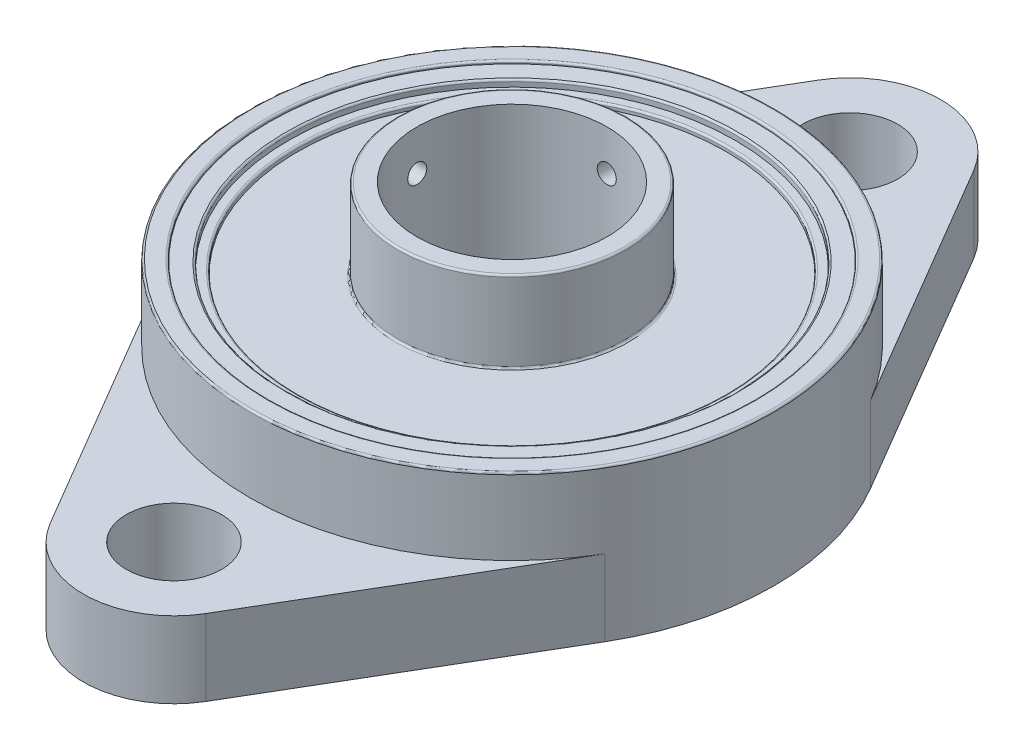
SolidWorks part; units mm, degrees
ref_plane "Front Plane" through (0, 0, 0) normal (0, 0, 1) x (1, 0, 0)
ref_plane "Top Plane" through (0, 0, 0) normal (0, 1, 0) x (1, 0, 0)
ref_plane "Right Plane" through (0, 0, 0) normal (1, 0, 0) x (0, 0, -1)
sketch "Sketch1" plane through (0, 0, 0) normal (0, 1, 0) x (1, 0, 0)
  line L0 (0, -45) -> (0, 45) construction
  line L1 (0, 0) -> (-50000, 0) construction
  line L2 (23.7028, -13.9437) -> (8.1883, -40.3169)
  line L3 (23.7028, 13.9437) -> (8.1883, 40.3169)
  line L4 (-23.7028, -13.9437) -> (-8.1883, -40.3169)
  line L5 (-23.7028, 13.9437) -> (-8.1883, 40.3169)
  circle A0 centre (0, 0) radius 27.5
  circle A1 centre (0, 0) radius 10
  circle A2 centre (0, 35.5) radius 5
  circle A3 centre (0, 0) radius 25.5
  circle A4 centre (0, 0) radius 12
  arc A5 (8.1883, 40.3169) -> (-8.1883, 40.3169) centre (0, 35.5) ccw
  circle A6 centre (0, -35.5) radius 5
  arc A7 (-8.1883, -40.3169) -> (8.1883, -40.3169) centre (0, -35.5) ccw
  circle A8 centre (0, 0) radius 23.5
  circle A9 centre (0, 0) radius 22.5
  point P6 (0, 0)
  dimension "D1" = 20
  dimension "D2" = 55
  dimension "D5" = 10
  dimension "D3" = 90
  dimension "D4" = 71
  dimension "D6" = 2
  dimension "D7" = 2
  dimension "D8" = 2
  dimension "D9" = 1
extrude "A1" add sketch "Sketch1" along normal blind 8 contours L4 A7 L2 A0 A6 | A0 A3 | L3 A5 L5 A0 A2 region at (15.4571, 0, 26.8429) region at (0, 0, 26.7222) region at (-15.4571, 0, -26.8429)
extrude "A" add sketch "Sketch1<3>" along normal blind 16 contours A0 A3 region at (0, 0, 26.7222)
sketch "Sketch1<3>" plane through (0, 0, 0) normal (0, 1, 0) x (1, 0, 0) same geometry as "Sketch1"
extrude "A0" add sketch "Sketch1<4>" along normal blind 23 contours A4 A1 region at (-11.6606, 0, 0)
sketch "Sketch1<4>" plane through (0, 0, 0) normal (0, 1, 0) x (1, 0, 0) same geometry as "Sketch1"
extrude "Bearing outer d" add sketch "Sketch1<7>" along normal blind 13 from offset 2 separate body contours A8 A9 region at (-22.8353, 0, 0)
sketch "Sketch1<7>" plane through (0, 0, 0) normal (0, 1, 0) x (1, 0, 0) same geometry as "Sketch1"
extrude "Boss-Extrude6" add sketch "Sketch1<8>" along normal blind 14.5 from offset 1.2 contours A3 A8 region at (-24.7788, 0, 0)
sketch "Sketch1<8>" plane through (0, 0, 0) normal (0, 1, 0) x (1, 0, 0) same geometry as "Sketch1"
extrude "Boss-Extrude7" add sketch "Sketch1<9>" along normal blind 13 from offset 1.5 contours A9 A4 region at (-21.8636, 0, 0)
sketch "Sketch1<9>" plane through (0, 0, 0) normal (0, 1, 0) x (1, 0, 0) same geometry as "Sketch1"
sketch "Sketch2" plane through (0, 0, 0) normal (1, 0, 0) x (0, 0, -1)
  line L0 (0, 0) -> (0, 50000) construction
  line L1 (-13.9437, 0) -> (13.9437, 0) construction
  line L2 (12, 18.75) -> (-12, 18.75) construction
  line L3 (12, 14.5) -> (12, 23) construction
  line L4 (-12, 23) -> (-12, 14.5) construction
  circle A0 centre (0, 18.75) radius 1
  point P4 (0, 0)
  dimension "D1" = 2
extrude "Cut-Extrude1" cut sketch "Sketch2" against normal up to next
sketch "Sketch3" plane through (0, 0, 0) normal (0, 0, 1) x (1, 0, 0)
  line L0 (0, 0) -> (0, 50000) construction
  line L1 (6, 18.75) -> (-49994, 18.75) construction
  line L3 (12, 14.5) -> (12, 23) construction
  circle A0 centre (0, 18.75) radius 1
  point P7 (12, 18.75)
  point P10 (0, 9.9)
  dimension "D1" = 2
extrude "Cut-Extrude2" cut sketch "Sketch3" against normal up to next
fillet "Fillet1" radius 0.2 1 edges at (0, 15, 22.5)
fillet "Fillet2" radius 0.2 5 edges at (0, 23, 12) (0, 14.5, 12) (0, 16, 27.5) (0, 16, 25.5) (0, 15.7, 23.5)
equation "\"A\"= \"D1@A\""
equation "\"A0\"= \"D1@A0\""
equation "\"A1\"= \"D1@A1\""
equation "\"D1@Bearing outer d\"=\"D1@Boss-Extrude6\" - 1.5"
equation "\"D1@Boss-Extrude6\"=\"D1@A\" - 1.5"
equation "\"D1@Boss-Extrude7\"= \"D1@Bearing outer d\""
equation "\"S\"= \"D19@Boss-Extrude7\""
equation "\"D19@Boss-Extrude6\"=\"D19@Boss-Extrude7\" - 0.3"
equation "\"H\"= \"D3@Sketch1\""
equation "\"J\"= \"D4@Sketch1\""
equation "\"L\"= \"D2@Sketch1\""
equation "\"N\"= \"D5@Sketch1\""
equation "\"d\"= \"D1@Sketch1\""
